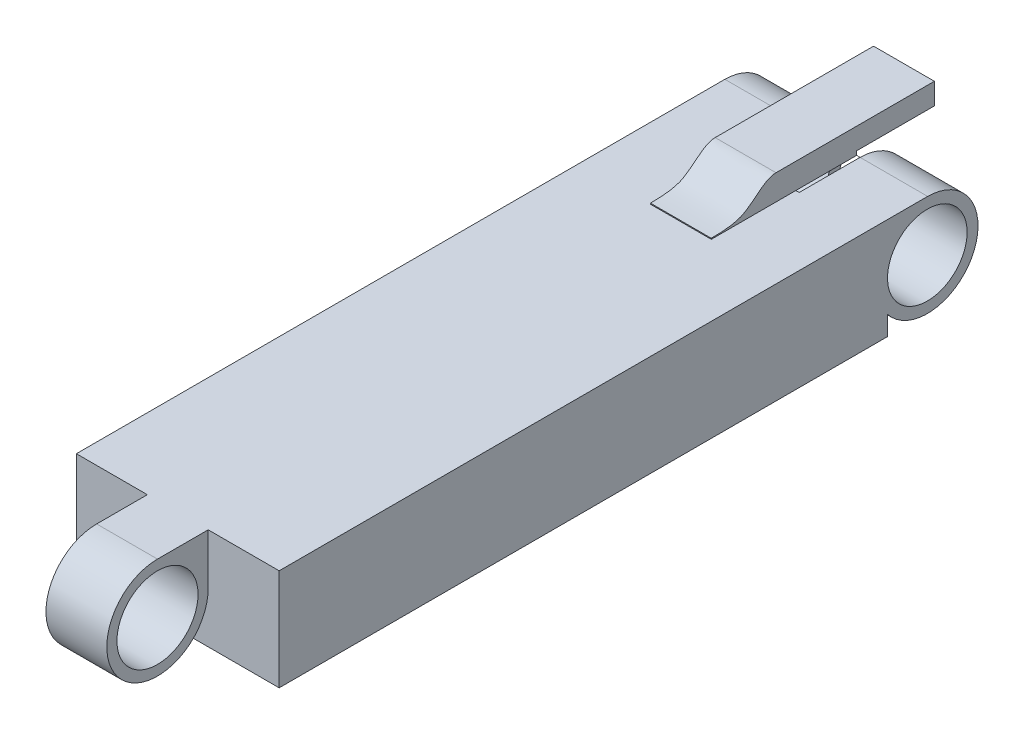
SolidWorks part; units mm, degrees
ref_plane "Front Plane" through (0, 0, 0) normal (0, 0, 1) x (1, 0, 0)
ref_plane "Top Plane" through (0, 0, 0) normal (0, 1, 0) x (1, 0, 0)
ref_plane "Right Plane" through (0, 0, 0) normal (1, 0, 0) x (0, 0, -1)
sketch "Sketch3" plane through (0, 0, 0) normal (1, 0, 0) x (0, 0, -1)
  line L0 (30, 2.5) -> (31.9626, 2.5) construction
  line L1 (0, 0) -> (30, 0)
  line L2 (0, 0) -> (0, 5)
  line L3 (0, 5) -> (30, 5)
  line L4 (30, 0) -> (30, 2.5)
  line L5 (30, 5) -> (31.9789, 5)
  line L6 (30, 5) -> (31.9789, 5)
  line L7 (31.9789, 5) -> (31.9626, 2.5)
  line L8 (31.9626, 2.5) -> (30, 2.5)
  dimension "D1" = 30
  dimension "D2" = 5
extrude "Boss-Extrude1" add sketch "Sketch3" along normal blind 10 contours L8 L7 L5 L3 L2 L1 L4 region at (0, 2.5398, -15.5084)
sketch "Sketch4" plane through (0, 0, 0) normal (1, 0, 0) x (0, 0, -1)
  circle A0 centre (31.9626, 2.5) radius 1.9626
sketch "Sketch6" plane through (0, 0, 0) normal (-1, 0, 0) x (0, 0, 1)
  circle A0 centre (-31.9626, 2.5) radius 2.5
  circle A1 centre (-31.9626, 2.5) radius 1.9626
extrude "Cut-Extrude2" cut sketch "Sketch4" along normal blind 10
extrude "Boss-Extrude2" add sketch "Sketch6" against normal blind 3.3333
sketch "Sketch7" plane through (10, 0, 0) normal (1, 0, 0) x (0, 0, -1)
  circle A0 centre (31.9626, 2.5) radius 1.9626
  circle A1 centre (31.9626, 2.5) radius 2.5
extrude "Boss-Extrude3" add sketch "Sketch7" against normal blind 3.3333
sketch "Sketch8" plane through (3.3333, 0, 0) normal (1, 0, 0) x (0, 0, -1)
  circle A0 centre (31.9626, 2.5) radius 1.9626
  circle A1 centre (31.9626, 2.5) radius 2.5
sketch "Sketch9" plane through (0, -0.2083, -31.945) normal (0, -0.0065, -1) x (-1, 0, 0)
  line L1 (-6.6667, 5.2084) -> (-3.3333, 5.2084)
  line L2 (-6.6667, 5.2084) -> (-6.6667, 0.2084)
  line L3 (-6.6667, 0.2084) -> (-3.3333, 0.2084)
  line L4 (-3.3333, 5.2084) -> (-3.3333, 0.2084)
extrude "Cut-Extrude7" cut sketch "Sketch9" against normal blind 3
sketch "Sketch10" plane through (0, 0.2084, -0.0014) normal (0, 1, -0.0065) x (1, 0, 0)
  line L1 (3.3333, 29.983) -> (6.6667, 29.983)
  line L2 (3.3333, 29.983) -> (3.3333, 28.9457)
  line L3 (3.3333, 28.9457) -> (6.6667, 28.9457)
  line L4 (6.6667, 29.983) -> (6.6667, 28.9457)
extrude "Cut-Extrude8" cut sketch "Sketch10" against normal through all
sketch "Sketch11" plane through (0, 5, 0) normal (0, 1, 0) x (1, 0, 0)
  line L0 (10, 0) -> (5, 0) construction
  line L1 (10, 0) -> (0, 0) construction
  line L2 (5, 0) -> (5, 6.4174) construction
ref_plane "Plane1" through (5, 0, 0) normal (1, 0, 0) x (0, 0, -1)
sketch "Sketch12" plane through (5, 0, 0) normal (1, 0, 0) x (0, 0, -1)
  line L0 (0, 2.5) -> (-2.5, 2.5) construction
  line L1 (0, 0) -> (0, 5) construction
  line L2 (-2.5, 5) -> (0, 5)
  line L3 (0, 5) -> (6.4174, 5) construction
  line L4 (0, 5) -> (0, 2.5)
  arc A0 (-2.5, 5) -> (0, 2.5) centre (-2.5, 2.5) ccw
  circle A1 centre (-2.5, 2.5) radius 2
extrude "Boss-Extrude4" add sketch "Sketch12" along normal blind 1.5 and the other way blind 1.5
sketch "Sketch13" plane through (5, 0, 0) normal (1, 0, 0) x (0, 0, -1)
  line L0 (30, 0.9514) -> (30, 5) construction
  line L1 (0, 5) -> (31.9789, 5) construction
  line L2 (30, 5) -> (28, 5) construction
  line L3 (24.8091, 5) -> (28, 5)
  line L4 (28, 5) -> (38, 5)
  line L6 (28, 6.25) -> (38, 6.25)
  line L7 (38, 5) -> (38, 6.25)
  line L8 (24.8091, 5) -> (24.8091, 5.047)
  spline S0 degree 3 poles (28, 6.25) (27.5701, 6.25) (27.108, 5.7874) (26.4447, 5.3239) (26.114, 5.047) (24.8091, 5.047) knots 0 0 0 0 0.435998 0.535998 1 1 1 1
  dimension "D1" = 10
  dimension "D2" = 1.25
  dimension "D3" = 0.047
  dimension "D4" = 24.8091
  dimension "D5" = 26.7894
  dimension "D6" = 28
  dimension "D7" = 5.5653
extrude "Boss-Extrude9" add sketch "Sketch13" along normal blind 1.5 and the other way blind 1.5
sketch "Sketch14" plane through (6.5, 0, 0) normal (1, 0, 0) x (0, 0, -1)
  line L0 (31.9789, 5) -> (31.9789, 5.197)
  line L1 (31.9789, 5.197) -> (35.811, 5.197)
  line L2 (38, 5) -> (38, 6.25) construction
  line L3 (38, 5.197) -> (38, 5)
  line L4 (38, 5) -> (31.9789, 5)
  line L5 (35.811, 5.197) -> (35.811, 6.25)
  line L6 (38, 6.25) -> (28, 6.25) construction
  line L7 (35.811, 6.25) -> (38, 6.25)
  line L8 (38, 6.25) -> (38, 5.197)
extrude "Cut-Extrude9" cut sketch "Sketch14" against normal through all
